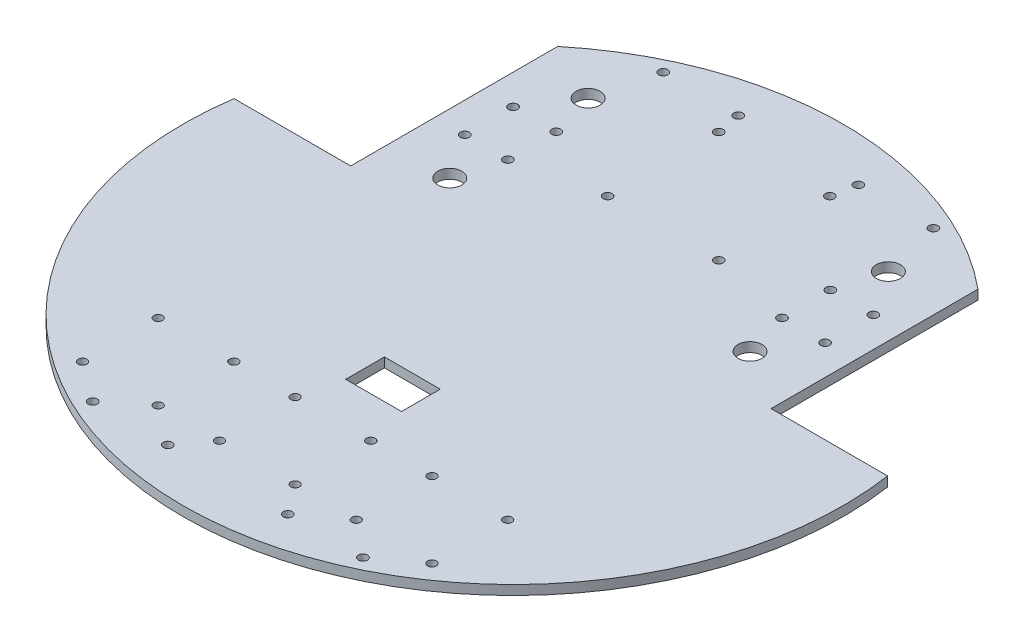
SolidWorks part; units mm, degrees
ref_plane "前视基准面" through (0, 0, 0) normal (0, 0, 1) x (1, 0, 0)
ref_plane "上视基准面" through (0, 0, 0) normal (0, 1, 0) x (1, 0, 0)
ref_plane "右视基准面" through (0, 0, 0) normal (1, 0, 0) x (0, 0, -1)
sketch "草图1" plane through (0, 0, 0) normal (0, 1, 0) x (1, 0, 0)
  line L0 (0, 0) -> (109.026, 0) construction
  line L5 (0, 0) -> (0, 50.562) construction
  line L13 (-9.3, -33.55) -> (9.3, -33.55)
  line L14 (-9.3, -33.55) -> (-9.3, -46.45)
  line L15 (-9.3, -46.45) -> (9.3, -46.45)
  line L16 (9.3, -33.55) -> (9.3, -46.45)
  line L17 (-9.3, -33.55) -> (9.3, -46.45) construction
  line L18 (-9.3, -46.45) -> (9.3, -33.55) construction
  line L19 (-108.8419, 15.92) -> (-70, 15.92)
  line L20 (-70, 84.8528) -> (-70, 15.92)
  line L21 (108.8419, 15.92) -> (70, 15.92)
  line L22 (70, 84.8528) -> (70, 15.92)
  circle A8 centre (-60, 43.92) radius 1.5
  circle A9 centre (-60, 60) radius 1.5
  circle A10 centre (-45.65, 60) radius 1.5
  circle A11 centre (-45.65, 43.92) radius 1.5
  circle A12 centre (60, 60) radius 1.5
  circle A13 centre (45.65, 60) radius 1.5
  circle A14 centre (45.65, 43.92) radius 1.5
  circle A15 centre (60, 43.92) radius 1.5
  circle A24 centre (-20, -95) radius 1.5
  circle A25 centre (20, -95) radius 1.5
  circle A26 centre (20, 95) radius 1.5
  circle A27 centre (-20, 95) radius 1.5
  circle A30 centre (-50, 75) radius 4
  circle A31 centre (50, 75) radius 4
  circle A36 centre (-18.5, 87) radius 1.5
  circle A39 centre (-18.5, 50) radius 1.5
  arc A40 (-108.8419, 15.92) -> (108.8419, 15.92) centre (0, 0) ccw
  circle A41 centre (18.5, 50) radius 1.5
  circle A42 centre (18.5, 87) radius 1.5
  circle A43 centre (-12.6, -60) radius 1.45
  circle A44 centre (-12.6, -85.2) radius 1.45
  circle A45 centre (12.6, -85.2) radius 1.45
  circle A46 centre (12.6, -60) radius 1.45
  circle A47 centre (-45, 95) radius 1.5
  circle A48 centre (45, 95) radius 1.5
  circle A49 centre (45, -95) radius 1.5
  circle A50 centre (-45, -95) radius 1.5
  circle A51 centre (-58.2, -60) radius 1.45
  circle A52 centre (-58.2, -85.2) radius 1.45
  circle A53 centre (-33, -60) radius 1.45
  circle A54 centre (-33, -85.2) radius 1.45
  circle A55 centre (58.2, -85.2) radius 1.45
  circle A56 centre (33, -85.2) radius 1.45
  circle A57 centre (33, -60) radius 1.45
  circle A58 centre (58.2, -60) radius 1.45
  circle A59 centre (-50, 28.92) radius 4
  circle A60 centre (50, 28.92) radius 4
  arc A61 (70, 84.8528) -> (-70, 84.8528) centre (0, 0) ccw
  point P0 (0, 0)
  point P43 (-110, 0)
  point P74 (0, -40)
  point P81 (0, 0)
  dimension "D3" = 14.35
  dimension "D4" = 16.08
  dimension "D6" = 3
  dimension "D8" = 220
  dimension "D9" = 8
  dimension "D10" = 100
  dimension "D15" = 3
  dimension "D17" = 2.9
  dimension "D22" = 40
  dimension "D24" = 95
  dimension "D11" = 3
  dimension "D25" = 3
  dimension "D26" = 20
  dimension "D30" = 33
  dimension "D5" = 60
  dimension "D7" = 50
  dimension "D12" = 37
  dimension "D13" = 37
  dimension "D14" = 95
  dimension "D16" = 20
  dimension "D18" = 25.2
  dimension "D19" = 18.6
  dimension "D20" = 12.9
  dimension "D21" = 25.2
  dimension "D23" = 45
  dimension "D27" = 50
  dimension "D28" = 15
  dimension "D29" = 25.2
  dimension "D32" = 10
  dimension "D33" = 28
  dimension "D34" = 15
extrude "Base" add sketch "草图1" along normal blind 3.175
